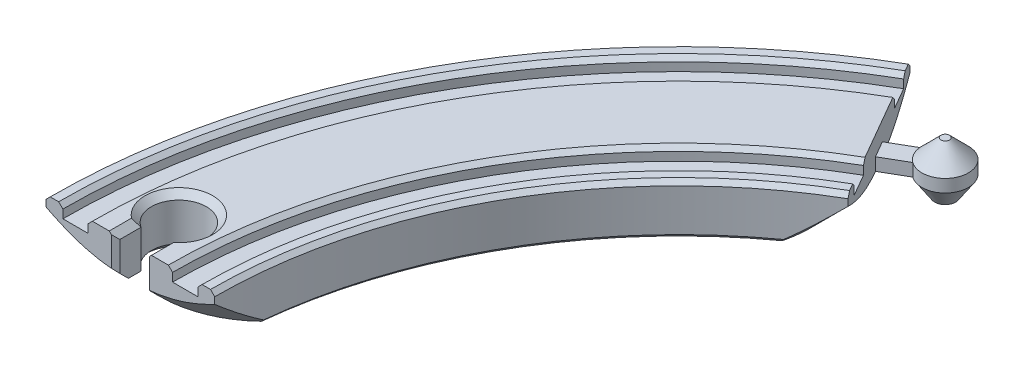
SolidWorks part; units mm, degrees
ref_plane "Front Plane" through (0, 0, 0) normal (0, 0, 1) x (1, 0, 0)
ref_plane "Top Plane" through (0, 0, 0) normal (0, 1, 0) x (1, 0, 0)
ref_plane "Right Plane" through (0, 0, 0) normal (1, 0, 0) x (0, 0, -1)
sketch "Sketch2" plane through (0, 0, 0) normal (0, 0, 1) x (1, 0, 0)
  line L0 (-20, 0) -> (20, 0)
  line L1 (20, 0) -> (20, 12)
  line L2 (20, 12) -> (16, 12)
  line L3 (16, 12) -> (16, 9)
  line L4 (16, 9) -> (10, 9)
  line L5 (10, 9) -> (10, 12)
  line L6 (10, 12) -> (-10, 12)
  line L7 (-10, 12) -> (-10, 9)
  line L8 (-10, 9) -> (-16, 9)
  line L9 (-16, 9) -> (-16, 12)
  line L10 (-16, 12) -> (-20, 12)
  line L11 (-20, 12) -> (-20, 0)
  line L12 (129.9038, 0) -> (129.9038, 12)
  point P4 (0, 0)
  dimension "D1" = 40
  dimension "D2" = 12
  dimension "D3" = 3
  dimension "D4" = 4
  dimension "D5" = 6
  dimension "D6" = 129.9038
revolve "Revolve1" add sketch "Sketch2" angle 60 about L12 region at (0, 5.6351, 0) reverse direction yes
sketch "Sketch3" plane through (0, 12, 0) normal (0, 1, 0) x (1, 0, 0)
  line L0 (10, 0) -> (-10, 0) construction
  line L2 (-3.5, 0) -> (3.5, 0)
  line L3 (-3.5, 0) -> (-3.5, 11.5)
  line L4 (-3.5, 11.5) -> (3.5, 11.5)
  line L5 (3.5, 0) -> (3.5, 11.5)
  line L6 (-3.5, 0) -> (3.5, 11.5) construction
  line L7 (-3.5, 11.5) -> (3.5, 0) construction
  circle A0 centre (0, 11.5) radius 6.5
  point P4 (0, 5.75)
  point P10 (0, 0)
  line M6 (-10, 0) -> (10, 0)
  dimension "D1" = 13
  dimension "D2" = 11.5
  dimension "D3" = 7
extrude "Cut-Extrude1" cut sketch "Sketch3" against normal through all contours L5 A0 L3 L4 | L3 A0 L5 L4 | A0 L3 L5 M6 region at (0, 12, -2.6732) region at (0, 12, -12.9919) region at (0, 12, -8.4074)
sketch "Sketch4" plane through (0, 12, 0) normal (0, 1, 0) x (1, 0, 0)
  line L0 (66.0769, 110.5514) -> (63.8269, 114.4486)
  line L1 (66.0769, 110.5514) -> (76.0362, 116.3014)
  line L2 (63.8269, 114.4486) -> (73.7862, 120.1986)
  line L3 (76.0362, 116.3014) -> (73.7862, 120.1986)
  line L4 (69.9519, 103.8397) -> (59.9519, 121.1603) construction
  circle A0 centre (74.9112, 118.25) radius 5.5
  point P9 (64.9519, 112.5)
  line M6 (69.9519, 103.8397) -> (59.9519, 121.1603)
  dimension "D1" = 11
  dimension "D2" = 4.5
  dimension "D3" = 11.5
extrude "Boss-Extrude1" add sketch "Sketch4" against normal up to surface (12 mm away) contours L1 A0 L2 L3 | L2 A0 L1 L3 region at (72.5962, 12, -116.9134) region at (75.6952, 12, -118.7026) up to face at (12.4699, 0, -33.3033)
extrude "Boss-Extrude2" add sketch "Sketch4<3>" against normal blind 7.5 contours A0 L2 L1 M6 region at (67.6196, 12, -114.0402)
sketch "Sketch4<3>" plane through (0, 12, 0) normal (0, 1, 0) x (1, 0, 0) same geometry as "Sketch4"
extrude "Cut-Extrude2" cut sketch "Sketch4<5>" against normal blind 4.5 contours A0 L2 L1 M6 region at (67.6196, 12, -114.0402)
sketch "Sketch4<5>" plane through (0, 12, 0) normal (0, 1, 0) x (1, 0, 0) same geometry as "Sketch4"
chamfer "Chamfer2" distance 4.5 angle 45 1 edges at (69.4112, 12, -118.25)
chamfer "Chamfer5" distance 3 distance2 4.5 1 edges at (74.9112, 0, -123.75) first distance on face at (74.9112, 0, -123.75)
chamfer "Chamfer3" distance 1.5 angle 45 6 edges at (0, 0, -18) (0, 12, -18) (3.5, 0, -3.0114) (-3.5, 0, -3.0114) (3.5, 12, -3.0114) (-3.5, 12, -3.0114)
sketch "Sketch17" plane through (-33.601, 0, -58.1986) normal (-0.5, 0, -0.866) x (-0.866, 0, 0.5)
  line L0 (-118.9813, 10.9813) -> (-118.9813, 0)
  line L1 (-118.9813, 0) -> (-108, 0)
  line L2 (-108, 0) -> (-118.9813, 10.9813)
  line L4 (-83, -1.2652) -> (-83, 10.9813) construction
  dimension "D1" = 25
revolve "Cut-Revolve1" cut sketch "Sketch17" angle 90 about L4
ref_plane "Plane1" through (-32.476, 0, -56.25) normal (-0.5, 0, -0.866) x (-0.866, 0, 0.5)
mirror "Mirror1" about plane through (-32.476, 0, -56.25) normal (-0.5, 0, -0.866) of "Cut-Revolve1"
chamfer "Chamfer4" distance 4.5 angle 45 1 edges at (64.9519, 0, -112.5)
ref_plane "Plane2" through (32.476, 0, -56.25) normal (0.5, 0, -0.866) x (-0.866, 0, -0.5)
mirror "Mirror4" about plane through (32.476, 0, -56.25) normal (0.5, 0, -0.866) of "Cut-Revolve1", "Mirror1"
chamfer "Chamfer1" distance 1 angle 45 10 edges at (34.7243, 12, -54.9519) (31.2602, 12, -56.9519) (26.0641, 12, -59.9519) (8.7436, 12, -69.9519) (3.5474, 12, -72.9519) (0.0833, 12, -74.9519) (34.7243, 0, -54.9519) (0.0833, 0, -74.9519) (3.5, 7.5132, 0) (-3.5, 7.5132, 0)
